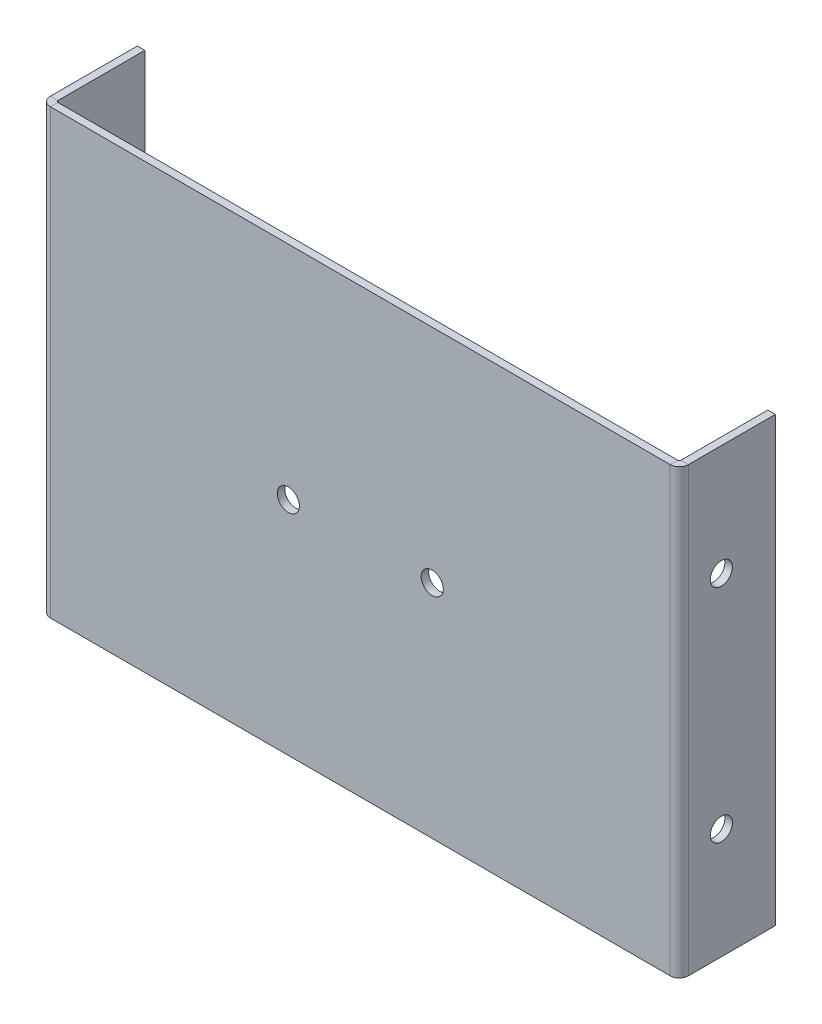
SolidWorks part; units mm, degrees
note: The reader was unsure of these and kept them because the rebuilt part matched: flange length of "Edge-Flange2", "Edge-Flange3".
material "1060 Alloy"
ref_plane "Front Plane" through (0, 0, 0) normal (0, 0, 1) x (1, 0, 0)
ref_plane "Top Plane" through (0, 0, 0) normal (0, 1, 0) x (1, 0, 0)
ref_plane "Right Plane" through (0, 0, 0) normal (1, 0, 0) x (0, 0, -1)
sketch "Sketch1" plane through (0, 0, 0) normal (0, 0, 1) x (1, 0, 0)
  line L0 (0, 0) -> (0, -200)
  line L1 (0, -200) -> (-288.2, -200)
  line L2 (-288.2, -200) -> (-288.2, 0)
  line L3 (-288.2, 0) -> (0, 0)
  line L4 (-144.1, 0) -> (-144.1, -200) construction
  line L5 (-288.2, -100) -> (0, -100) construction
  circle A0 centre (-111.6, -100) radius 5
  circle A1 centre (-176.6, -100) radius 5
  dimension "D3" = 10
  dimension "D1" = 288.2
  dimension "D2" = 200
  dimension "D4" = 32.5
base flange "Base-Flange1" sketch "Sketch1" thickness 3.4 reverse thickness direction no parameters "D1"=0.7366
edge flange "Edge-Flange2" sketch "Sketch7" flange angle 90 flange length 43.4 flange position material inside bend radius 0.7366 thickness 3.4 relief rectangular parameters "D6"=10
sketch "Sketch7" plane through (0, 0, -3.4) normal (1, 0, 0) x (0, -1, 0)
  line L0 (200, 0) -> (0, 0) construction
  line L1 (200, 0) -> (0, 0)
  line L2 (0, 0) -> (0, 40)
  line L3 (0, 40) -> (200, 40)
  line L4 (200, 40) -> (200, 0)
  line L5 (100, 0) -> (100, 15.6) construction
  line L6 (100, 15.6) -> (50, 15.6) construction
  circle A0 centre (50, 15.6) radius 5
  circle A1 centre (150, 15.6) radius 5
  dimension "D3" = 10
  dimension "D1" = 40
  dimension "D2" = 19
  dimension "D4" = 50
bend "EdgeBend2" bend radius 0.7366 bend angle 90 parameters "D5"=1
edge flange "Edge-Flange3" sketch "Sketch10" flange angle 90 flange length 43.4 flange position material inside bend radius 0.7366 thickness 3.4 relief rectangular parameters "D6"=10
sketch "Sketch10" plane through (-288.2, 0, -3.4) normal (-1, 0, 0) x (0, 1, 0)
  line L0 (0, 0) -> (-200, 0) construction
  line L1 (0, 0) -> (-200, 0)
  line L2 (-200, 0) -> (-200, 40)
  line L3 (-200, 40) -> (0, 40)
  line L4 (0, 40) -> (0, 0)
  line L5 (-100, 0) -> (-100, 40) construction
  line L6 (0, -3.4) -> (-200, -3.4) construction
  circle A0 centre (-50, 15.6) radius 5
  circle A1 centre (-150, 15.6) radius 5
  dimension "D1" = 10
  dimension "D4" = 40
  dimension "D2" = 50
  dimension "D3" = 19
bend "EdgeBend3" bend radius 0.7366 bend angle 90 parameters "D5"=2
sketch "Bend-Lines1" [suppressed] plane through (0, 0, 0) normal (0, 1, 0) x (1, 0, 0)
sketch "Bounding-Box1" [suppressed] plane through (0, 0, 0) normal (0, 1, 0) x (1, 0, 0)
sheet metal parameters "Sheet-Metal1" thickness 3.4 parameters "D1"=0.7366
flat pattern "Flat-Pattern1" [suppressed]
sketch "Bend-Lines2" plane through (0, 0, 0) normal (0, 1, 0) x (1, 0, 0)
sketch3d "Bounding-Box2" [suppressed]
  line L0 (-295, -200, 0) -> (0, -200, 0) construction
  line L1 (-295, 0, 0) -> (0, 0, 0) construction
  line L2 (-295, -200, 0) -> (-295, 0, 0) construction
  line L3 (0, -200, 0) -> (0, 0, 0) construction
sheet metal parameters "Sheet-Metal3" thickness 3.4 parameters "D1"=0.7366
flat pattern "Flat-Pattern1"
sketch "Bend-Lines2" plane through (0, 0, 0) normal (0, 0, 1) x (1, 0, 0)
  line L0 (-2.2229, -200) -> (-2.2229, 0) construction
  line L1 (-2.2229, -200) -> (-2.2229, 0) construction
sketch3d "Bounding-Box2" [suppressed]
  line L0 (-295, -200, 0) -> (35.5542, -200, 0) construction
  line L1 (-295, 0, 0) -> (35.5542, 0, 0) construction
  line L2 (-295, -200, 0) -> (-295, 0, 0) construction
  line L3 (35.5542, -200, 0) -> (35.5542, 0, 0) construction
bend of the flat pattern "Flatten-<EdgeBend2>1"
sheet metal parameters "Sheet-Metal4" thickness 3.4 parameters "D1"=0.7366
flat pattern "Flat-Pattern1"
sketch "Bend-Lines2" plane through (0, 0, 0) normal (0, 0, 1) x (1, 0, 0)
  line L0 (-2.2229, -200) -> (-2.2229, 0) construction
  line L1 (-2.2229, -200) -> (-2.2229, 0) construction
  line L2 (-285.9771, 0) -> (-285.9771, -200) construction
  line L3 (-285.9771, 0) -> (-285.9771, -200) construction
sketch3d "Bounding-Box2" [suppressed]
  line L0 (-327.1542, -200, 0) -> (38.9542, -200, 0) construction
  line L1 (-327.1542, 0, 0) -> (38.9542, 0, 0) construction
  line L2 (-327.1542, -200, 0) -> (-327.1542, 0, 0) construction
  line L3 (38.9542, -200, 0) -> (38.9542, 0, 0) construction
bend of the flat pattern "Flatten-<EdgeBend2>1"
bend of the flat pattern "Flatten-<EdgeBend3>1"
